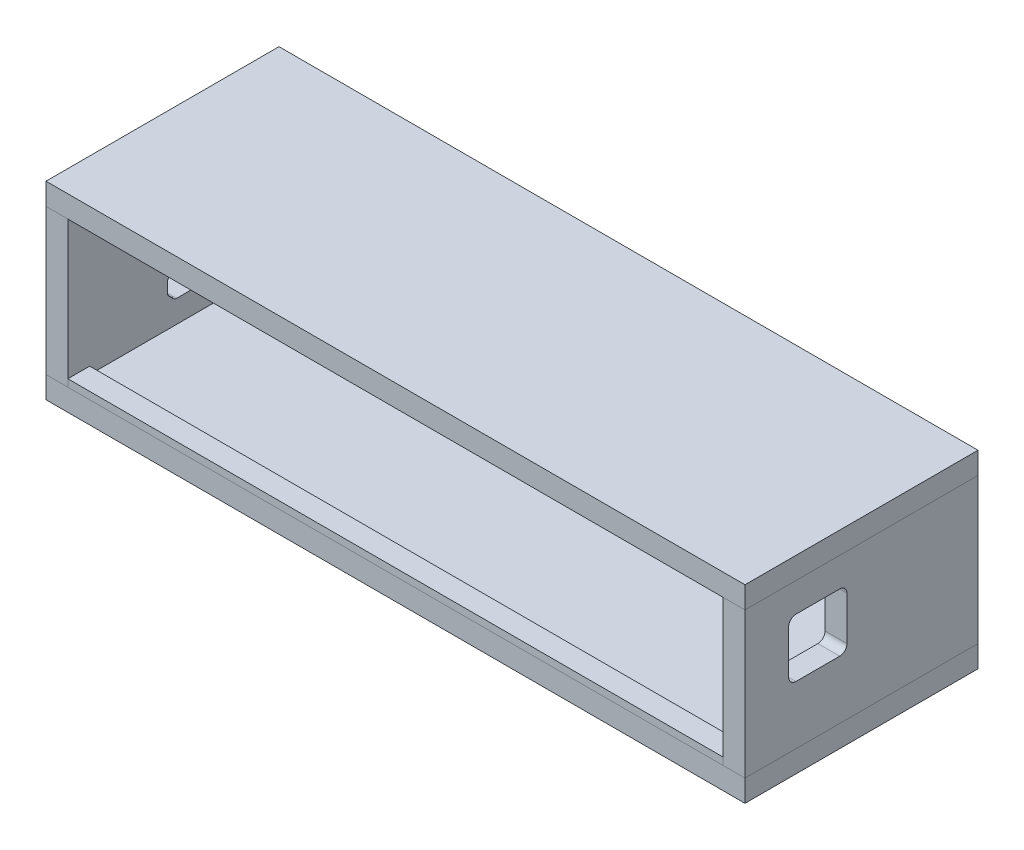
SolidWorks part; units mm, degrees
ref_plane "Front Plane" through (0, 0, 0) normal (0, 0, 1) x (1, 0, 0)
ref_plane "Top Plane" through (0, 0, 0) normal (0, 1, 0) x (1, 0, 0)
ref_plane "Right Plane" through (0, 0, 0) normal (1, 0, 0) x (0, 0, -1)
sketch "Sketch1" plane through (0, 0, 0) normal (0, 1, 0) x (1, 0, 0)
  line L1 (-304.8, 101.6) -> (304.8, 101.6)
  line L2 (-304.8, 101.6) -> (-304.8, -101.6)
  line L3 (-304.8, -101.6) -> (304.8, -101.6)
  line L4 (304.8, 101.6) -> (304.8, -101.6)
  line L5 (-304.8, 101.6) -> (304.8, -101.6) construction
  line L6 (-304.8, -101.6) -> (304.8, 101.6) construction
  point P0 (0, 0)
  dimension "D1" = 609.6
  dimension "D2" = 203.2
extrude "Boss-Extrude1" add sketch "Sketch1" along normal blind 19.05
sketch "Sketch2" plane through (0, 19.05, 0) normal (0, 1, 0) x (1, 0, 0)
  line L0 (-304.8, -101.6) -> (304.8, -101.6) construction
  line L1 (-304.8, 101.6) -> (-285.75, 101.6)
  line L2 (-304.8, 101.6) -> (-304.8, -101.6)
  line L3 (-304.8, -101.6) -> (-285.75, -101.6)
  line L4 (-285.75, 101.6) -> (-285.75, -101.6)
  line L5 (304.8, 101.6) -> (-304.8, 101.6) construction
  line L6 (304.8, -101.6) -> (285.75, -101.6)
  line L7 (304.8, -101.6) -> (304.8, 101.6)
  line L8 (304.8, 101.6) -> (285.75, 101.6)
  line L9 (285.75, -101.6) -> (285.75, 101.6)
  line L11 (-285.75, 101.6) -> (285.75, 101.6)
  line L12 (-285.75, 101.6) -> (-285.75, 82.55)
  line L13 (-285.75, 82.55) -> (285.75, 82.55)
  line L14 (285.75, 101.6) -> (285.75, 82.55)
  line M7 (304.8, -101.6) -> (304.8, 101.6)
  line M8 (304.8, 101.6) -> (-304.8, 101.6)
  line M9 (-304.8, 101.6) -> (-304.8, -101.6)
  line M10 (-304.8, -101.6) -> (304.8, -101.6)
  dimension "D1" = 19.05
  dimension "D2" = 19.05
  dimension "D3" = 19.05
extrude "Boss-Extrude2" add sketch "Sketch2" along normal blind 127 separate body contours L4 M8 M9 M10 | L9 M10 M7 M8 region at (-295.275, 19.05, 0) region at (295.275, 19.05, 0)
extrude "Boss-Extrude3" add sketch "Sketch2<3>" along normal up to surface (127 mm away) separate body contours L4 L13 L9 M8 region at (0, 19.05, -92.075) up to face at (-295.275, 146.05, 0)
sketch "Sketch2<3>" plane through (0, 19.05, 0) normal (0, 1, 0) x (1, 0, 0) same geometry as "Sketch2"
sketch "Sketch3" plane through (0, 146.05, 0) normal (0, 1, 0) x (1, 0, 0)
  line L1 (-304.8, 101.6) -> (304.8, 101.6)
  line L2 (-304.8, 101.6) -> (-304.8, -101.6)
  line L3 (-304.8, -101.6) -> (304.8, -101.6)
  line L4 (304.8, 101.6) -> (304.8, -101.6)
extrude "Boss-Extrude4" add sketch "Sketch3" along normal blind 19.05 separate body
sketch "Sketch4" plane through (0, 19.05, 0) normal (0, 1, 0) x (1, 0, 0)
  line L0 (285.75, -101.6) -> (285.75, 101.6) construction
  line L1 (-285.75, -101.6) -> (285.75, -101.6)
  line L2 (-285.75, -101.6) -> (-285.75, -82.55)
  line L3 (-285.75, -82.55) -> (285.75, -82.55)
  line L4 (285.75, -101.6) -> (285.75, -82.55)
  dimension "D1" = 19.05
extrude "Boss-Extrude5" add sketch "Sketch4" along normal blind 6.35 separate body
sketch "Sketch5" plane through (-304.8, 0, -304.8) normal (1, 0, 0) x (0, 0, -1)
  line L0 (-203.2, 82.55) -> (-406.4, 82.55) construction
  line L1 (-203.2, 146.05) -> (-203.2, 19.05) construction
  line L2 (-406.4, 146.05) -> (-406.4, 19.05) construction
  line L3 (-304.8, 82.55) -> (-304.8, 19.05) construction
  line L4 (-203.2, 19.05) -> (-406.4, 19.05) construction
  line L26 (-295.1743, 39.8975) -> (-291.0923, 43.9795)
  line L27 (-289.9361, 46.7691) -> (-289.9361, 54.4059)
  line L28 (-295.9636, 60.4385) -> (-313.5841, 60.4385)
  line L29 (-319.6321, 54.3905) -> (-319.6321, 46.8124)
  line L30 (-318.4465, 43.95) -> (-314.4246, 39.9281)
  line L31 (-311.5622, 38.7425) -> (-309.7841, 38.7425)
  line L32 (-309.7841, 38.7425) -> (-299.7841, 38.7425)
  line L33 (-299.7841, 38.7425) -> (-297.9644, 38.7425)
  spline S18 degree 3 poles (-291.0923, 43.9795) (-291.0033, 44.0735) (-290.9158, 44.1689) (-290.7535, 44.3694) (-290.6774, 44.4737) (-290.4636, 44.7979) (-290.3426, 45.0263) (-290.1465, 45.4989) (-290.0705, 45.7454) (-289.9923, 46.1261) (-289.9724, 46.2537) (-289.9454, 46.5104) (-289.9398, 46.6397) (-289.9361, 46.7691) knots 0 0 0 0 0.125 0.125 0.25 0.25 0.5 0.5 0.75 0.75 0.875 0.875 1 1 1 1
  spline S19 degree 3 poles (-289.9361, 54.4059) (-289.9381, 54.6045) (-289.9467, 54.8019) (-289.9861, 55.1929) (-290.0151, 55.3868) (-290.0921, 55.7711) (-290.1401, 55.9616) (-290.2552, 56.3393) (-290.3228, 56.5272) (-290.5499, 57.0745) (-290.7344, 57.4205) (-291.1705, 58.0741) (-291.4251, 58.3841) (-291.9809, 58.9409) (-292.2833, 59.191) (-292.7753, 59.5217) (-292.9465, 59.6247) (-293.2946, 59.8114) (-293.4723, 59.8957) (-294.0155, 60.1225) (-294.3917, 60.2394) (-294.9766, 60.3577) (-295.1726, 60.3872) (-295.5666, 60.4274) (-295.7648, 60.4358) (-295.9636, 60.4385) knots 0 0 0 0 0.0625 0.0625 0.125 0.125 0.1875 0.1875 0.25 0.25 0.375 0.375 0.5 0.5 0.625 0.625 0.6875 0.6875 0.75 0.75 0.875 0.875 0.9375 0.9375 1 1 1 1
  spline S20 degree 3 poles (-313.5841, 60.4385) (-313.9834, 60.4385) (-314.376, 60.3998) (-314.9552, 60.2847) (-315.1466, 60.2368) (-315.5262, 60.1217) (-315.7149, 60.0541) (-316.2641, 59.827) (-316.6115, 59.6419) (-317.2686, 59.2036) (-317.5795, 58.9479) (-318.1377, 58.3905) (-318.3886, 58.0866) (-318.7204, 57.5913) (-318.8233, 57.4195) (-319.0098, 57.0704) (-319.094, 56.8921) (-319.3205, 56.3466) (-319.4373, 55.9666) (-319.5935, 55.185) (-319.6321, 54.7899) (-319.6321, 54.3905) knots 0 0 0 0 0.125 0.125 0.1875 0.1875 0.25 0.25 0.375 0.375 0.5 0.5 0.625 0.625 0.6875 0.6875 0.75 0.75 0.875 0.875 1 1 1 1
  spline S21 degree 3 poles (-319.6321, 46.8124) (-319.6321, 46.5457) (-319.6061, 46.2818) (-319.5017, 45.7593) (-319.4244, 45.5064) (-319.2237, 45.0204) (-319.0984, 44.7849) (-318.8033, 44.3432) (-318.6351, 44.1386) (-318.4465, 43.95) knots 0 0 0 0 0.25 0.25 0.5 0.5 0.75 0.75 1 1 1 1
  spline S22 degree 3 poles (-314.4246, 39.9281) (-314.236, 39.7395) (-314.0309, 39.5713) (-313.5877, 39.2757) (-313.3542, 39.1515) (-312.8686, 38.9498) (-312.6135, 38.8719) (-312.0925, 38.7682) (-311.8289, 38.7425) (-311.5622, 38.7425) knots 0 0 0 0 0.25 0.25 0.5 0.5 0.75 0.75 1 1 1 1
  spline S23 degree 3 poles (-297.9644, 38.7425) (-297.8349, 38.746) (-297.7057, 38.7516) (-297.4491, 38.7786) (-297.3215, 38.7985) (-296.9411, 38.8766) (-296.6941, 38.9525) (-296.2213, 39.1481) (-295.9932, 39.2686) (-295.6687, 39.4825) (-295.5644, 39.5587) (-295.3638, 39.7211) (-295.2684, 39.8086) (-295.1743, 39.8975) knots 0 0 0 0 0.125 0.125 0.25 0.25 0.5 0.5 0.75 0.75 0.875 0.875 1 1 1 1
  point P11 (-304.7739, 60.4385)
extrude "Cut-Extrude1" cut sketch "Sketch5" along normal up to surface (19.05 mm away) up to face at (-285.75, 82.55, 0)
sketch "Sketch6" plane through (0, 0, -82.55) normal (0, 0, 1) x (1, 0, 0)
  line L0 (-285.75, 146.05) -> (285.75, 146.05) construction
  line L1 (133.35, 107.95) -> (234.95, 107.95)
  line L2 (133.35, 107.95) -> (133.35, 57.15)
  line L3 (133.35, 57.15) -> (234.95, 57.15)
  line L4 (234.95, 107.95) -> (234.95, 57.15)
  line L5 (133.35, 107.95) -> (234.95, 57.15) construction
  line L6 (133.35, 57.15) -> (234.95, 107.95) construction
  line L7 (285.75, 146.05) -> (285.75, 19.05) construction
  point P0 (184.15, 82.55)
  dimension "D1" = 63.5
  dimension "D2" = 50.8
  dimension "D3" = 101.6
  dimension "D4" = 50.8
extrude "Cut-Extrude2" cut sketch "Sketch6" against normal through all
sketch "Sketch9" plane through (0, 0, -82.55) normal (0, 0, 1) x (1, 0, 0)
  line L0 (-285.75, 19.05) -> (285.75, 19.05) construction
  line L1 (-254.8532, 120.05) -> (-179.8532, 120.05)
  line L2 (-254.8532, 120.05) -> (-254.8532, 45.05)
  line L3 (-254.8532, 45.05) -> (-179.8532, 45.05)
  line L4 (-179.8532, 120.05) -> (-179.8532, 45.05)
  line L5 (-254.8532, 120.05) -> (-179.8532, 45.05) construction
  line L6 (-254.8532, 45.05) -> (-179.8532, 120.05) construction
  point P0 (-217.3532, 82.55)
  dimension "D1" = 75
  dimension "D2" = 75
  dimension "D3" = 63.5
extrude "Cut-Extrude3" cut sketch "Sketch9" against normal through all
sketch "Sketch10" plane through (285.75, 0, 0) normal (-1, 0, 0) x (0, 0, 1)
  line L0 (101.6, 146.05) -> (-101.6, 146.05) construction
  line L1 (12.7, 120.65) -> (63.5, 120.65)
  line L2 (12.7, 120.65) -> (12.7, 69.85)
  line L3 (12.7, 69.85) -> (63.5, 69.85)
  line L4 (63.5, 120.65) -> (63.5, 69.85)
  line L5 (12.7, 120.65) -> (63.5, 69.85) construction
  line L6 (12.7, 69.85) -> (63.5, 120.65) construction
  line L7 (101.6, 146.05) -> (101.6, 19.05) construction
  point P0 (38.1, 95.25)
  dimension "D1" = 50.8
  dimension "D2" = 50.8
  dimension "D3" = 50.8
  dimension "D5" = 38.1
extrude "Cut-Extrude4" cut sketch "Sketch10" against normal through all
fillet "Fillet1" radius 6.35 8 edges at (234.95, 107.95, -92.075) (234.95, 57.15, -92.075) (133.35, 57.15, -92.075) (133.35, 107.95, -92.075) (-254.8532, 45.05, -92.075) (-179.8532, 45.05, -92.075) (-254.8532, 120.05, -92.075) (-179.8532, 120.05, -92.075)
fillet "Fillet2" radius 6.35 4 edges at (295.275, 120.65, 63.5) (295.275, 69.85, 63.5) (295.275, 69.85, 12.7) (295.275, 120.65, 12.7)
